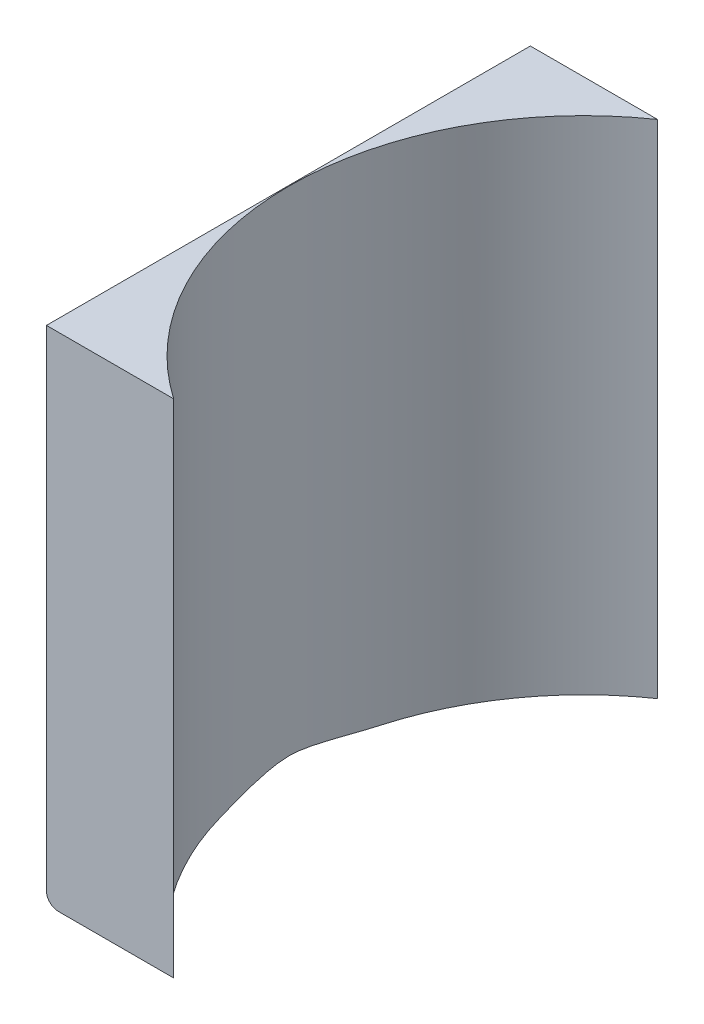
SolidWorks part; units mm, degrees
material "Бутил"
ref_plane "Спереди" through (0, 0, 0) normal (0, 0, 1) x (1, 0, 0)
ref_plane "Сверху" through (0, 0, 0) normal (0, 1, 0) x (1, 0, 0)
ref_plane "Справа" through (0, 0, 0) normal (1, 0, 0) x (0, 0, -1)
other "Configuration Table"
sketch "Эскиз1" plane through (0, 0, 0) normal (0, 1, 0) x (1, 0, 0)
  line L1 (12.5, -20.5) -> (-12.5, -20.5)
  line L2 (12.5, -20.5) -> (12.5, 20.5)
  line L3 (12.5, 20.5) -> (-12.5, 20.5)
  line L4 (-12.5, -20.5) -> (-12.5, 20.5)
  line L5 (12.5, -20.5) -> (-12.5, 20.5) construction
  line L6 (12.5, 20.5) -> (-12.5, -20.5) construction
  point P0 (0, 0)
  dimension "D1" = 25
  dimension "D2" = 41
extrude "Бобышка-Вытянуть1" add sketch "Эскиз1" along normal blind 42.5
fillet "Скругление1" radius 1 1 edges at (-12.5, 0, 0)
sketch "Эскиз2" plane through (0, 42.5, 0) normal (0, 1, 0) x (1, 0, 0)
  line L0 (12.5, -20.5) -> (12.5, 20.5) construction
  circle A0 centre (12.5, 0) radius 24.95
  dimension "D1" = 49.9
extrude "Вырез-Вытянуть1" cut sketch "Эскиз2" against normal blind 42.5
